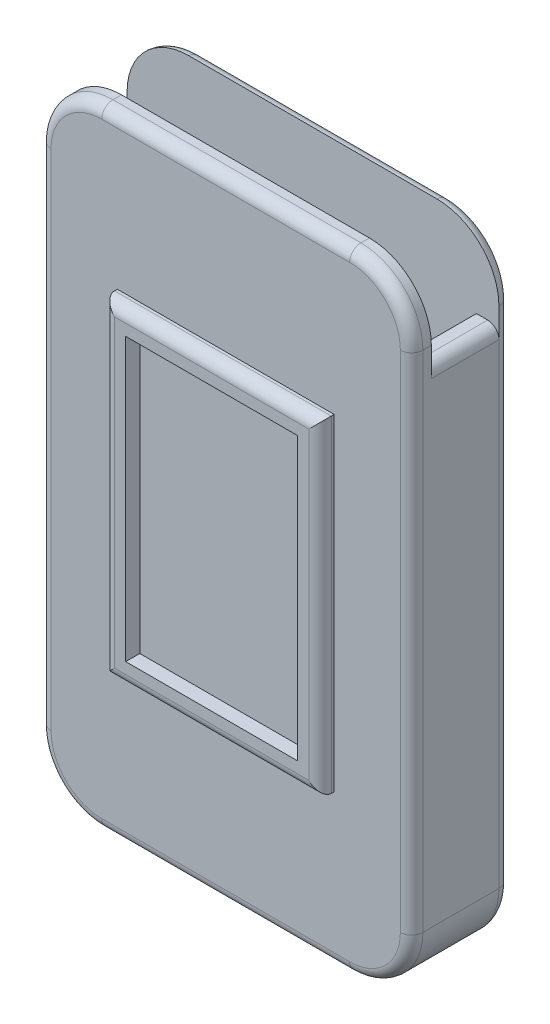
SolidWorks part; units mm, degrees
ref_plane "Alzado" through (0, 0, 0) normal (0, 0, 1) x (1, 0, 0)
ref_plane "Planta" through (0, 0, 0) normal (0, 1, 0) x (1, 0, 0)
ref_plane "Vista lateral" through (0, 0, 0) normal (1, 0, 0) x (0, 0, -1)
sketch "Croquis1" plane through (0, 0, 0) normal (0, 0, 1) x (1, 0, 0)
  line L0 (56.9343, 22.5676) -> (100.9343, 22.5676)
  line L1 (107.9343, 29.5676) -> (107.9343, 119.0676)
  line L2 (100.9343, 126.0676) -> (56.9343, 126.0676)
  line L3 (49.9343, 119.0676) -> (49.9343, 29.5676)
  line L4 (56.9343, 108.0676) -> (56.9343, 29.5676)
  line L5 (100.9343, 108.0676) -> (100.9343, 29.5676)
  line L6 (56.9343, 108.0676) -> (100.9343, 108.0676)
  line L7 (56.9343, 29.5676) -> (100.9343, 29.5676)
  line L8 (56.9343, 130.0676) -> (100.9343, 130.0676)
  line L9 (45.9343, 29.5676) -> (45.9343, 119.0676)
  line L10 (56.9343, 18.5676) -> (100.9343, 18.5676)
  line L11 (111.9343, 29.5676) -> (111.9343, 119.0676)
  arc A0 (49.9343, 29.5676) -> (56.9343, 22.5676) centre (56.9343, 29.5676) ccw
  arc A1 (100.9343, 22.5676) -> (107.9343, 29.5676) centre (100.9343, 29.5676) ccw
  arc A2 (107.9343, 119.0676) -> (100.9343, 126.0676) centre (100.9343, 119.0676) ccw
  arc A3 (56.9343, 126.0676) -> (49.9343, 119.0676) centre (56.9343, 119.0676) ccw
  arc A4 (111.9343, 119.0676) -> (100.9343, 130.0676) centre (100.9343, 119.0676) ccw
  arc A5 (56.9343, 130.0676) -> (45.9343, 119.0676) centre (56.9343, 119.0676) ccw
  arc A6 (100.9343, 18.5676) -> (111.9343, 29.5676) centre (100.9343, 29.5676) ccw
  arc A7 (45.9343, 29.5676) -> (56.9343, 18.5676) centre (56.9343, 29.5676) ccw
  dimension "D1" = 78.5
  dimension "D2" = 44
extrude "Saliente-Extruir1" add sketch "Croquis1" along normal blind 2 contours L2 A3 L3 A0 L0 A1 L1 A2 L7 L4 L6 L5 | L9 A7 L10 A6 L11 A4 L8 A5 A3 L2 A2 L1 A1 L0 A0 L3 region at (52.8235, 25.4568, 0) region at (78.9343, 128.7719, 0)
sketch "Croquis2" plane through (0, 0, 2) normal (0, 0, 1) x (1, 0, 0)
  line L0 (56.9343, 22.5676) -> (100.9343, 22.5676)
  line L1 (45.9343, 29.5676) -> (45.9343, 115.9414)
  line L2 (49.9343, 29.5676) -> (49.9343, 115.9414)
  line L3 (107.9343, 29.5676) -> (107.9343, 115.9414)
  line L4 (56.9343, 108.0676) -> (56.9343, 29.5676)
  line L5 (100.9343, 108.0676) -> (100.9343, 29.5676)
  line L6 (56.9343, 108.0676) -> (100.9343, 108.0676)
  line L7 (56.9343, 29.5676) -> (100.9343, 29.5676)
  line L8 (111.9343, 29.5676) -> (111.9343, 115.9414)
  line L10 (56.9343, 18.5676) -> (100.9343, 18.5676)
  line L13 (49.9343, 115.9414) -> (45.9343, 115.9414)
  line L14 (107.9343, 115.9414) -> (111.9343, 115.9414)
  arc A0 (49.9343, 29.5676) -> (56.9343, 22.5676) centre (56.9343, 29.5676) ccw
  arc A1 (100.9343, 22.5676) -> (107.9343, 29.5676) centre (100.9343, 29.5676) ccw
  arc A6 (100.9343, 18.5676) -> (111.9343, 29.5676) centre (100.9343, 29.5676) ccw
  arc A7 (45.9343, 29.5676) -> (56.9343, 18.5676) centre (56.9343, 29.5676) ccw
  line M5 (45.9343, 119.0676) -> (45.9343, 29.5676)
  arc M6 (45.9343, 29.5676) -> (56.9343, 18.5676) centre (56.9343, 29.5676) ccw
  line M7 (56.9343, 18.5676) -> (100.9343, 18.5676)
  arc M8 (100.9343, 18.5676) -> (111.9343, 29.5676) centre (100.9343, 29.5676) ccw
  line M9 (111.9343, 29.5676) -> (111.9343, 119.0676)
  arc M10 (111.9343, 119.0676) -> (100.9343, 130.0676) centre (100.9343, 119.0676) ccw
  line M11 (100.9343, 130.0676) -> (56.9343, 130.0676)
  arc M12 (56.9343, 130.0676) -> (45.9343, 119.0676) centre (56.9343, 119.0676) ccw
  dimension "D1" = 78.5
  dimension "D2" = 44
extrude "Saliente-Extruir2" add sketch "Croquis2" along normal blind 12 contours A1 L0 A0 M12 M5 M6 M7 M8 M9 M10 M11 region at (78.9343, 21.3913, 2)
sketch "Croquis3" plane through (0, 0, 14) normal (0, 0, 1) x (1, 0, 0)
  line L0 (56.9343, 22.5676) -> (100.9343, 22.5676)
  line L1 (107.9343, 29.5676) -> (107.9343, 119.0676)
  line L2 (100.9343, 126.0676) -> (56.9343, 126.0676)
  line L3 (49.9343, 119.0676) -> (49.9343, 29.5676)
  line L4 (56.9343, 108.0676) -> (56.9343, 29.5676)
  line L5 (100.9343, 108.0676) -> (100.9343, 29.5676)
  line L6 (56.9343, 108.0676) -> (100.9343, 108.0676)
  line L7 (56.9343, 29.5676) -> (100.9343, 29.5676)
  line L8 (56.9343, 130.0676) -> (100.9343, 130.0676)
  line L9 (45.9343, 29.5676) -> (45.9343, 119.0676)
  line L10 (56.9343, 18.5676) -> (100.9343, 18.5676)
  line L11 (111.9343, 29.5676) -> (111.9343, 119.0676)
  arc A0 (49.9343, 29.5676) -> (56.9343, 22.5676) centre (56.9343, 29.5676) ccw
  arc A1 (100.9343, 22.5676) -> (107.9343, 29.5676) centre (100.9343, 29.5676) ccw
  arc A2 (107.9343, 119.0676) -> (100.9343, 126.0676) centre (100.9343, 119.0676) ccw
  arc A3 (56.9343, 126.0676) -> (49.9343, 119.0676) centre (56.9343, 119.0676) ccw
  arc A4 (111.9343, 119.0676) -> (100.9343, 130.0676) centre (100.9343, 119.0676) ccw
  arc A5 (56.9343, 130.0676) -> (45.9343, 119.0676) centre (56.9343, 119.0676) ccw
  arc A6 (100.9343, 18.5676) -> (111.9343, 29.5676) centre (100.9343, 29.5676) ccw
  arc A7 (45.9343, 29.5676) -> (56.9343, 18.5676) centre (56.9343, 29.5676) ccw
  arc M1 (107.9343, 29.5676) -> (100.9343, 22.5676) centre (100.9343, 29.5676) cw
  line M2 (100.9343, 22.5676) -> (56.9343, 22.5676)
  arc M3 (56.9343, 22.5676) -> (49.9343, 29.5676) centre (56.9343, 29.5676) cw
  line M4 (49.9343, 29.5676) -> (49.9343, 115.9414)
  line M5 (49.9343, 115.9414) -> (45.9343, 115.9414)
  line M6 (45.9343, 115.9414) -> (45.9343, 29.5676)
  arc M7 (45.9343, 29.5676) -> (56.9343, 18.5676) centre (56.9343, 29.5676) ccw
  line M8 (56.9343, 18.5676) -> (100.9343, 18.5676)
  arc M9 (100.9343, 18.5676) -> (111.9343, 29.5676) centre (100.9343, 29.5676) ccw
  line M10 (111.9343, 29.5676) -> (111.9343, 115.9414)
  line M11 (111.9343, 115.9414) -> (107.9343, 115.9414)
  line M12 (107.9343, 115.9414) -> (107.9343, 29.5676)
  dimension "D1" = 78.5
  dimension "D2" = 44
extrude "Saliente-Extruir3" add sketch "Croquis3" along normal blind 3.5 contours L8 A5 L9 L3 A3 L2 A2 L1 L11 A4 M5 M11 | M12 M1 M2 M3 M4 M5 M6 M7 M8 M9 M10 M11 | L2 A3 L3 L1 A2 L7 L4 L6 L5 M4 M3 M2 M1 M12 | L4 L7 L5 L6 region at (52.8235, 25.4568, 14) region at (78.9343, 21.3913, 14) region at (78.9343, 126.083, 14) region at (78.9343, 68.8176, 14)
sketch "Croquis4" plane through (0, 0, 17.5) normal (0, 0, 1) x (1, 0, 0)
  line L0 (63.6843, 49.3176) -> (94.1843, 49.3176)
  line L1 (56.9343, 18.5676) -> (100.9343, 18.5676) construction
  line L2 (45.9343, 29.5676) -> (45.9343, 119.0676) construction
  line L3 (63.6843, 99.3176) -> (94.1843, 99.3176)
  line L4 (63.6843, 99.3176) -> (59.6843, 99.3176)
  line L5 (59.6843, 99.3176) -> (59.6843, 45.3176)
  line L6 (59.6843, 45.3176) -> (98.1843, 45.3176)
  line L7 (98.1843, 45.3176) -> (98.1843, 103.3176)
  line L8 (98.1843, 103.3176) -> (59.6843, 103.3176)
  line L9 (63.6843, 49.3176) -> (63.6843, 99.3176)
  line L10 (94.1843, 99.3176) -> (94.1843, 49.3176)
  line L11 (59.6843, 103.3176) -> (59.6843, 99.3176)
  dimension "D1" = 30.5
  dimension "D2" = 50
  dimension "D3" = 30.75
  dimension "D4" = 17.75
  dimension "D5" = 4
  dimension "D6" = 4
  dimension "D7" = 4
  dimension "D8" = 4
extrude "Saliente-Extruir4" add sketch "Croquis4" along normal blind 2.5 contours L8 L11 L3 L10 L0 L9 L5 L6 L7 region at (60.3804, 101.3176, 17.5)
sketch "Croquis5" plane through (0, 0, 0) normal (0, 0, -1) x (-1, 0, 0)
  line L0 (-56.9343, 108.0676) -> (-45.9343, 108.0676)
  line L1 (-45.9343, 29.5676) -> (-45.9343, 119.0676) construction
  line L2 (-45.9343, 108.0676) -> (-45.9343, 101.0676)
  dimension "D1" = 7
sketch "Croquis6" plane through (45.9343, 0, 0) normal (-1, 0, 0) x (0, 0, 1)
  line L0 (2, 101.0676) -> (14, 101.0676)
  line L2 (2, 115.9414) -> (2, 101.0676)
  line L3 (14, 115.9414) -> (14, 101.0676)
  line L4 (2, 115.9414) -> (14, 115.9414)
  dimension "D1" = 14.8738
extrude "Cortar-Extruir3" cut sketch "Croquis6" against normal blind 4
fillet "Redondeo2" radius 2 8 edges at (78.9343, 18.5676, 0) (108.7124, 21.7894, 0) (111.9343, 74.3176, 0) (108.7124, 126.8458, 0) (78.9343, 130.0676, 0) (49.1561, 126.8458, 0) (45.9343, 74.3176, 0) (49.1561, 21.7894, 0)
fillet "Redondeo3" radius 2 8 edges at (49.1561, 21.7894, 17.5) (45.9343, 74.3176, 17.5) (49.1561, 126.8458, 17.5) (78.9343, 130.0676, 17.5) (108.7124, 126.8458, 17.5) (111.9343, 74.3176, 17.5) (108.7124, 21.7894, 17.5) (78.9343, 18.5676, 17.5)
fillet "Redondeo4" radius 2 4 edges at (59.6843, 74.3176, 20) (78.9343, 45.3176, 20) (98.1843, 74.3176, 20) (78.9343, 103.3176, 20)
fillet "Redondeo5" radius 2 1 edges at (45.9343, 101.0676, 8)
fillet "Redondeo6" radius 2 1 edges
